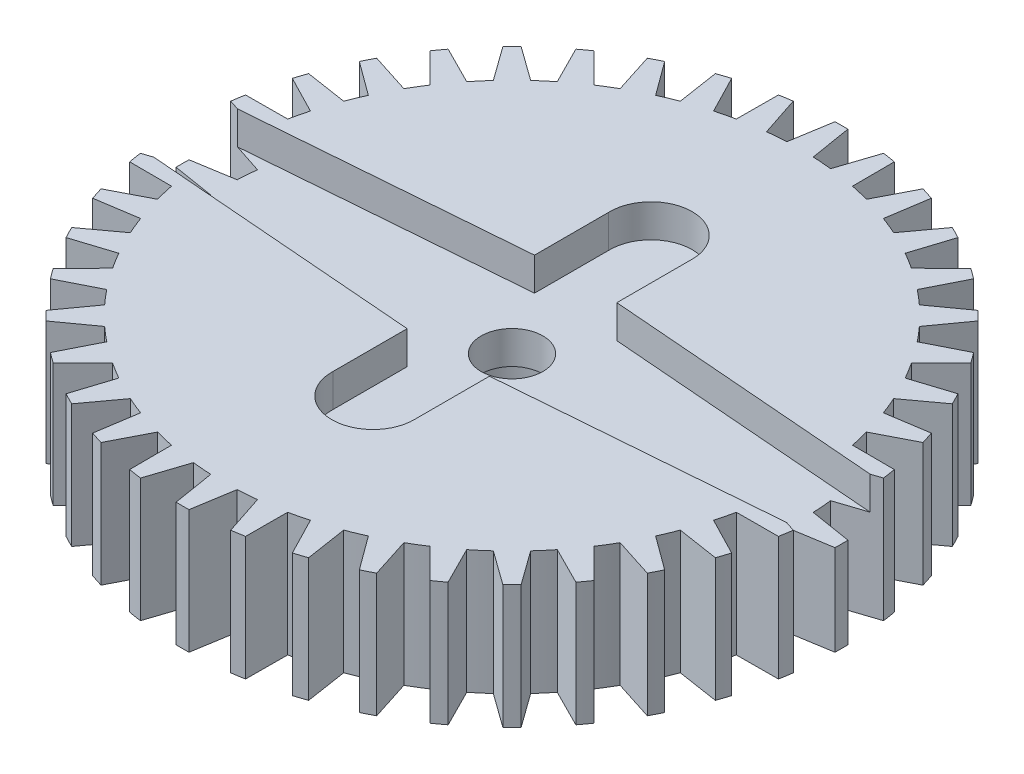
SolidWorks part; units mm, degrees
ref_plane "Front Plane" through (0, 0, 0) normal (0, 0, 1) x (1, 0, 0)
ref_plane "Top Plane" through (0, 0, 0) normal (0, 1, 0) x (1, 0, 0)
ref_plane "Right Plane" through (0, 0, 0) normal (1, 0, 0) x (0, 0, -1)
sketch "Sketch1" plane through (0, 0, 0) normal (0, 1, 0) x (1, 0, 0)
  circle A0 centre (0, 0) radius 1.5
  circle A1 centre (0, 0) radius 16
  dimension "D1" = 3
  dimension "D2" = 32
extrude "Boss-Extrude1" add sketch "Sketch1" along normal blind 6
sketch "Sketch2" plane through (0, 6, 0) normal (0, 1, 0) x (1, 0, 0)
  line L0 (0, 0) -> (0, 15.5) construction
  line L1 (0, 0) -> (-0.3141, 15.9969) construction
  line L2 (0, 0) -> (-0.6412, 13.9853) construction
  line L3 (0, 0) -> (-1.0984, 13.9568) construction
  line L4 (-0.6412, 13.9853) -> (-0.3141, 15.9969)
  line L5 (0.6412, 13.9853) -> (0.3141, 15.9969)
  line L6 (-1.0984, 13.9568) -> (-1.346, 17.1025)
  line L7 (-1.346, 17.1025) -> (1.346, 17.1025)
  line L8 (1.346, 17.1025) -> (1.0984, 13.9568)
  circle A0 centre (0, 0) radius 16 construction
  arc A1 (0.3141, 15.9969) -> (-0.3141, 15.9969) centre (0, 0) ccw
  arc A3 (-0.6412, 13.9853) -> (-1.0984, 13.9568) centre (0, 0) ccw
  arc A4 (0.6412, 13.9853) -> (1.0984, 13.9568) centre (0, 0) cw
  dimension "D4" = 14
  dimension "D1" = 1.125
  dimension "D2" = 1.5
  dimension "D3" = 1.875
extrude "Cut-Extrude1" cut sketch "Sketch2" against normal up to next (6 mm away)
pattern_circular "CirPattern1" count 40 over 360 about axis through (0, 6, 0) along (0, -1, 0) of "Cut-Extrude1" reverse direction yes
sketch "Sketch3" plane through (0, 6, 0) normal (0, 1, 0) x (1, 0, 0)
  line L0 (15.75, 0) -> (-15.75, 0) construction
  line L1 (0, -6.75) -> (0, 6.75) construction
  line L2 (-1.8988, 6.6833) -> (-1.8988, 3)
  line L3 (1.8988, 6.6833) -> (1.8988, 3)
  line L4 (-15.75, 1.9) -> (-1.8988, 3)
  line L5 (15.75, 1.9) -> (1.8988, 3)
  line L6 (15.75, -1.9) -> (1.8988, -3)
  line L7 (1.8988, -6.6833) -> (1.8988, -3)
  line L8 (-1.8988, -6.6833) -> (-1.8988, -3)
  line L9 (-15.75, -1.9) -> (-1.8988, -3)
  line L10 (-1.9988, 6.6816) -> (-1.9988, 3.0924)
  line L11 (-15.754, 2) -> (-1.9988, 3.0924)
  line L12 (-15.754, -2) -> (-1.9988, -3.0924)
  line L13 (-1.9988, -6.6816) -> (-1.9988, -3.0924)
  line L14 (1.9988, -6.6816) -> (1.9988, -3.0924)
  line L15 (15.754, -2) -> (1.9988, -3.0924)
  line L16 (15.754, 2) -> (1.9988, 3.0924)
  line L17 (1.9988, 6.6816) -> (1.9988, 3.0924)
  circle A0 centre (0, 0) radius 1.25
  arc A1 (-1.8988, 6.6833) -> (1.8988, 6.6833) centre (0, 6.75) cw
  arc A2 (-15.75, 1.9) -> (-15.75, -1.9) centre (-15.75, 0) ccw
  arc A3 (15.75, 1.9) -> (15.75, -1.9) centre (15.75, 0) cw
  arc A4 (-1.8988, -6.6833) -> (1.8988, -6.6833) centre (0, -6.75) ccw
  arc A5 (-15.754, 2) -> (-15.754, -2) centre (-15.75, 0) ccw
  arc A6 (-1.9988, -6.6816) -> (1.9988, -6.6816) centre (0, -6.75) ccw
  arc A7 (15.754, 2) -> (15.754, -2) centre (15.75, 0) cw
  arc A8 (-1.9988, 6.6816) -> (1.9988, 6.6816) centre (0, 6.75) cw
  point P5 (0, 0)
  point P8 (0, 0)
  point P20 (-0.466, 4.749)
  point P21 (0, 0)
  point P22 (0, 0)
  point P23 (-0.466, 4.749)
  point P24 (0, 0)
  dimension "D1" = 2.5
  dimension "D4" = 1.9
  dimension "D5" = 1.9
  dimension "D2" = 13.5
  dimension "D3" = 31.5
  dimension "D6" = 1.1
  dimension "D7" = 0.1
extrude "Cut-Extrude2" cut sketch "Sketch3" against normal blind 1.6 contours A8 L10 L11 A5 L12 L13 A6 L14 L15 A7 L16 L17 A4 L8 L9 A2 L4 L2 A1 L3 L5 A3 L6 L7 | L8 A4 L7 L6 A3 L5 L3 A1 L2 L4 A2 L9 A0 region at (0, 6, -8.2569) region at (0, 6, -8.7104)
sketch "Sketch4" plane through (0, 0, 0) normal (0, -1, 0) x (1, 0, 0)
  circle A0 centre (0, 0) radius 2.5
  dimension "D1" = 5
extrude "Cut-Extrude3" cut sketch "Sketch4" against normal offset from surface (2.8 mm away) 1.6 up to face at (0, 4.4, 1.5)
equation "\"num_teeth\" = 40"
equation "\"D1@Sketch2\"=(1.5/6)*(360 / \"num_teeth\")*0.5"
equation "\"D2@Sketch2\"=(2/6)*(360 / \"num_teeth\")*0.5"
equation "\"D3@Sketch2\"=(2.5/6)*(360 / \"num_teeth\")*0.5"
equation "\"D1@CirPattern1\"=\"num_teeth\""
equation "\"diameter\" = 30mm"
equation "\"D2@Sketch1\"=\"diameter\" + 2"
equation "\"D4@Sketch2\"=(\"diameter\" / 2) - 1"
